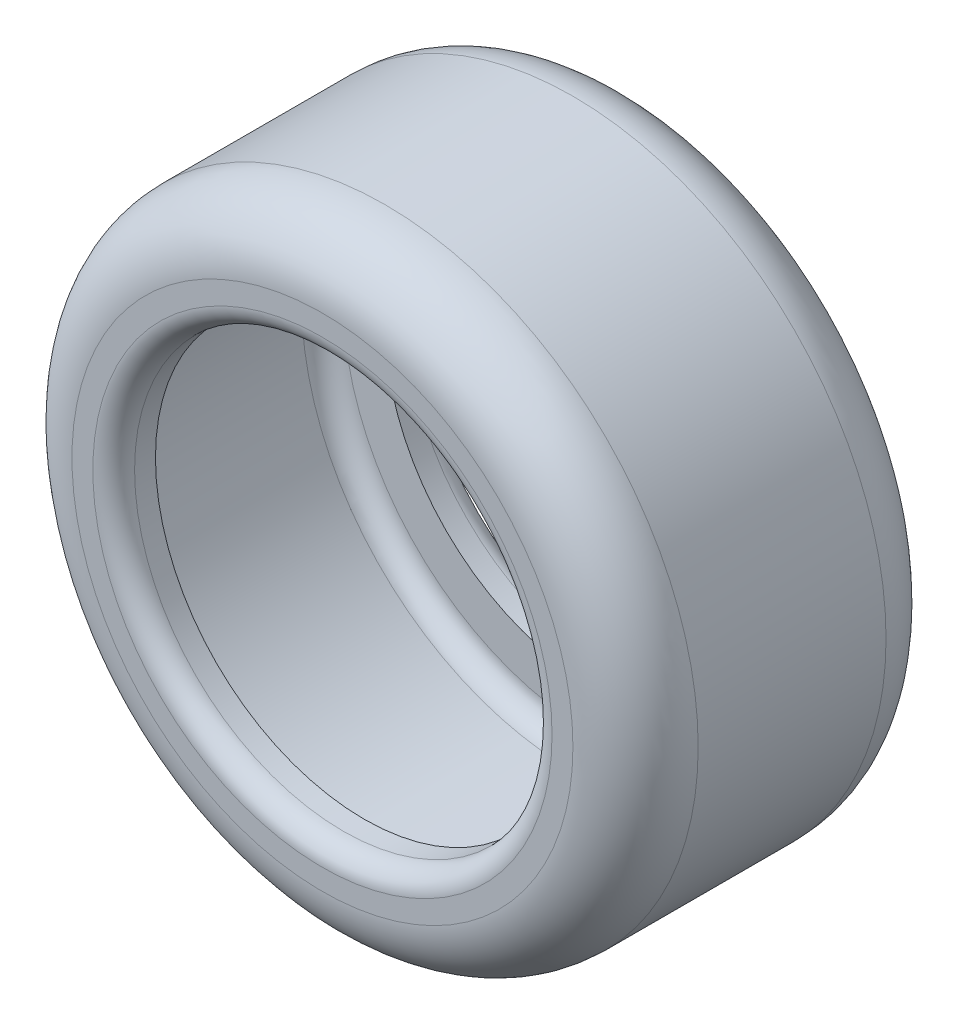
SolidWorks part; units mm, degrees
ref_plane "Front Plane" through (0, 0, 0) normal (0, 0, 1) x (1, 0, 0)
ref_plane "Top Plane" through (0, 0, 0) normal (0, 1, 0) x (1, 0, 0)
ref_plane "Right Plane" through (0, 0, 0) normal (1, 0, 0) x (0, 0, -1)
sketch "Sketch2" plane through (0, 0, 0) normal (0, 0, 1) x (1, 0, 0)
  circle A0 centre (0, 0) radius 100
  dimension "D1" = 200
extrude "Extrude-Thin1" add sketch "Sketch2" along normal blind 150 thin thin type one direction wall 50
fillet "Fillet1" radius 30 2 edges at (150, 0, 0) (150, 0, 150)
fillet "Fillet2" radius 10 2 edges at (100, 0, 0) (100, 0, 150)
shell "Shell1" thickness 20 removed face at (100, 0, 10)
